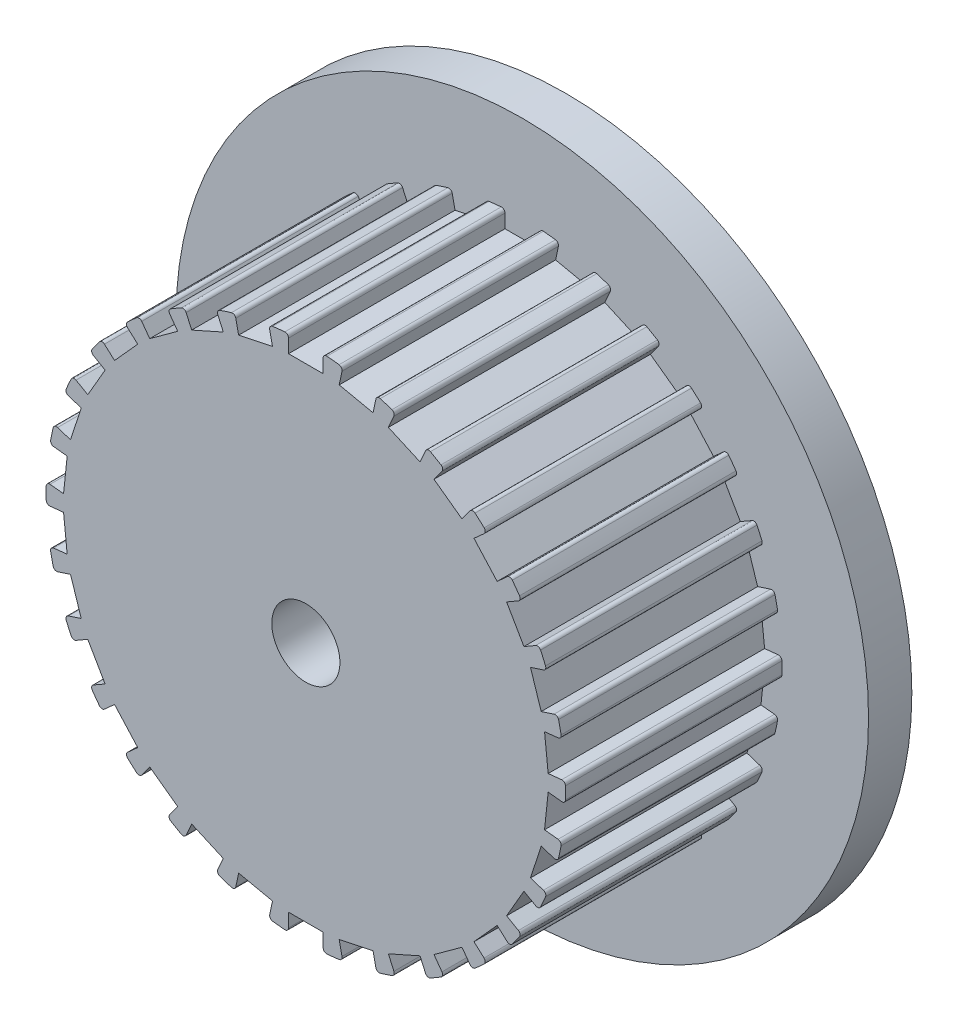
SolidWorks part; units mm, degrees
ref_plane "Front Plane" through (0, 0, 0) normal (0, 0, 1) x (1, 0, 0)
ref_plane "Top Plane" through (0, 0, 0) normal (0, 1, 0) x (1, 0, 0)
ref_plane "Right Plane" through (0, 0, 0) normal (1, 0, 0) x (0, 0, -1)
sketch "Sketch1" plane through (0, 0, 0) normal (0, 0, 1) x (1, 0, 0)
  circle A0 centre (0, 0) radius 12.7
  dimension "D1" = 25.4
extrude "Boss-Extrude1" add sketch "Sketch1" along normal blind 1.5875
sketch "Sketch2" plane through (0, 0, 1.5875) normal (0, 0, 1) x (1, 0, 0)
  circle A0 centre (0, 0) radius 9.525
  dimension "D1" = 19.05
extrude "Boss-Extrude2" add sketch "Sketch2" along normal blind 7.9375
sketch "Sketch3" plane through (0, 0, 9.525) normal (0, 0, 1) x (1, 0, 0)
  circle A0 centre (0, 0) radius 1.25
  dimension "D1" = 2.5
extrude "Cut-Extrude1" cut sketch "Sketch3" against normal through all
sketch "Sketch4" plane through (0, 0, 9.525) normal (0, 0, 1) x (1, 0, 0)
  line L0 (0, 8.8688) -> (0, 9.525) construction
  line L6 (-0.635, 9.5038) -> (0.635, 9.5038)
  line L7 (-0.635, 9.5038) -> (-0.635, 10.1388)
  line L8 (-0.635, 10.1388) -> (0.635, 10.1388)
  line L9 (0.635, 9.5038) -> (0.635, 10.1388)
  line L10 (-0.635, 9.5038) -> (0.635, 9.5038)
  line L11 (-0.635, 9.5038) -> (-0.635, 8.8688)
  line L12 (-0.635, 8.8688) -> (0.635, 8.8688)
  line L13 (0.635, 9.5038) -> (0.635, 8.8688)
  circle A0 centre (0, 0) radius 9.525 construction
  circle A5 centre (0, 0) radius 9.525 construction
  point P13 (0, 9.4966)
  dimension "D1" = 1.27
  dimension "D2" = 0.635
  dimension "D4" = 0.635
extrude "Cut-Extrude2" cut sketch "Sketch4" against normal up to surface (7.9375 mm away) contours L12 L13 L10 L11 | L7 L6 L9 L8 up to face at (9.525, 0, 1.5875)
fillet "Fillet2" radius 0.127 2 edges at (0.635, 9.5038, 5.5563) (-0.635, 9.5038, 5.5563)
pattern_circular "CirPattern1" count 30 over 360 about axis through (0, 0, 1.5875) along (0, 0, 1) of "Cut-Extrude2", "Fillet2"
